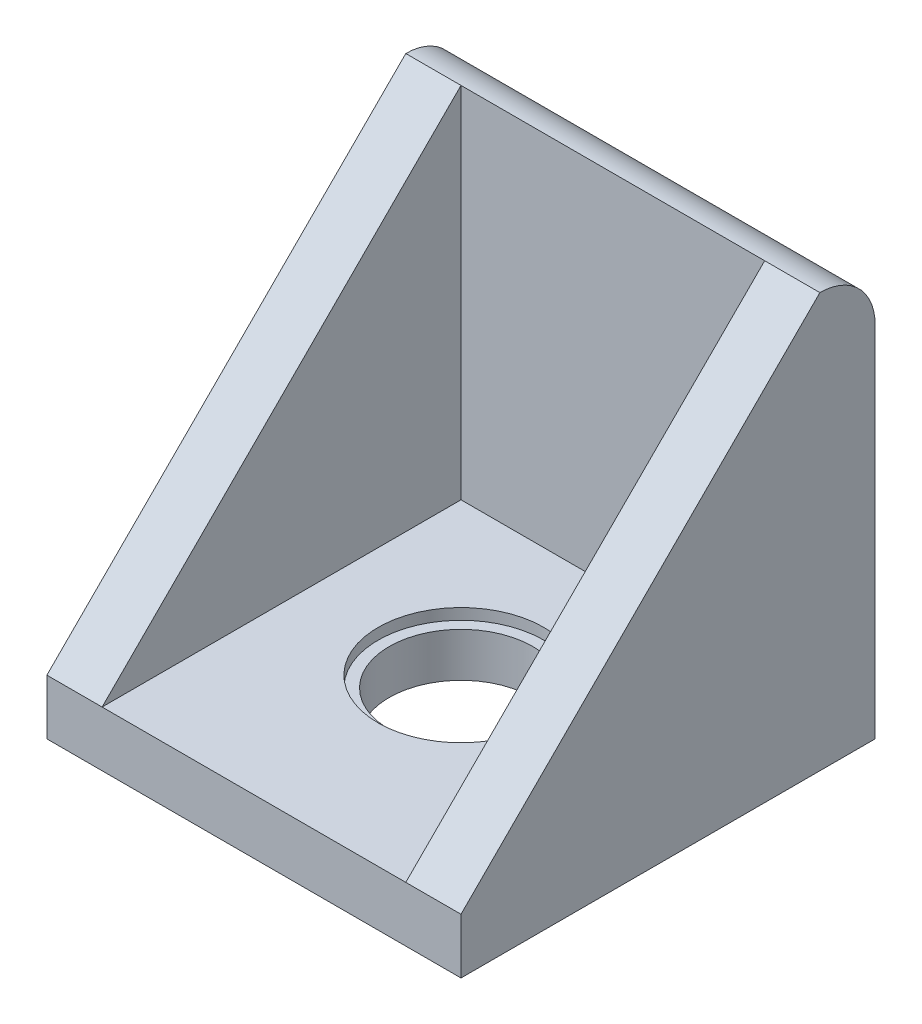
SolidWorks part; units mm, degrees
ref_plane "Front Plane" through (0, 0, 0) normal (0, 0, 1) x (1, 0, 0)
ref_plane "Top Plane" through (0, 0, 0) normal (0, 1, 0) x (1, 0, 0)
ref_plane "Right Plane" through (0, 0, 0) normal (1, 0, 0) x (0, 0, -1)
sketch "Sketch1" plane through (0, 0, 0) normal (0, 1, 0) x (1, 0, 0)
  line L1 (-3.75, 3.75) -> (3.75, 3.75)
  line L2 (-3.75, 3.75) -> (-3.75, -3.75)
  line L3 (-3.75, -3.75) -> (3.75, -3.75)
  line L4 (3.75, 3.75) -> (3.75, -3.75)
  line L5 (-3.75, 3.75) -> (3.75, -3.75) construction
  line L6 (-3.75, -3.75) -> (3.75, 3.75) construction
  point P0 (0, 0)
  dimension "D1" = 7.5
  dimension "D2" = 7.5
extrude "Boss-Extrude1" add sketch "Sketch1" along normal blind 7.5
sketch "Sketch2" plane through (0, 7.5, 0) normal (0, 1, 0) x (1, 0, 0)
  line L0 (-3.75, -3.75) -> (3.75, -3.75) construction
  line L1 (-2.75, -3.75) -> (2.75, -3.75)
  line L2 (-2.75, -3.75) -> (-2.75, 2.75)
  line L3 (-2.75, 2.75) -> (2.75, 2.75)
  line L4 (2.75, -3.75) -> (2.75, 2.75)
  line L5 (3.75, 3.75) -> (-3.75, 3.75) construction
  line L6 (-3.75, 3.75) -> (-3.75, -3.75) construction
  line L7 (3.75, -3.75) -> (3.75, 3.75) construction
  dimension "D1" = 1
  dimension "D2" = 1
  dimension "D3" = 1
extrude "Cut-Extrude1" cut sketch "Sketch2" against normal blind 6.5
sketch "Sketch3" plane through (3.75, 0, 0) normal (1, 0, 0) x (0, 0, -1)
  line L7 (-3.75, 7.5) -> (2.75, 7.5)
  line L8 (-3.75, 7.5) -> (3.75, 7.5) construction
  line L9 (2.75, 7.5) -> (-3.75, 1)
  line L10 (-3.75, 7.5) -> (-3.75, 0) construction
  line L11 (-3.75, 1) -> (-3.75, 7.5)
  dimension "D1" = 1
  dimension "D2" = 1
extrude "Cut-Extrude2" cut sketch "Sketch3" against normal up to surface (7.5 mm away) up to face at (-3.75, 3.75, 0)
sketch "Sketch4" plane through (0, 0, 0) normal (0, -1, 0) x (1, 0, 0)
  circle A0 centre (0, 0) radius 1.3
  dimension "D1" = 2.6
extrude "Cut-Extrude3" cut sketch "Sketch4" against normal up to surface (1 mm away) up to face at (0, 1, 0.5)
sketch "Sketch5" plane through (0, 1, 0) normal (0, 1, 0) x (1, 0, 0)
  circle A0 centre (0, 0) radius 1.5
  dimension "D1" = 3
extrude "Cut-Extrude4" cut sketch "Sketch5" against normal blind 0.2
fillet "Fillet1" radius 1 1 edges at (0, 7.5, -3.75)
